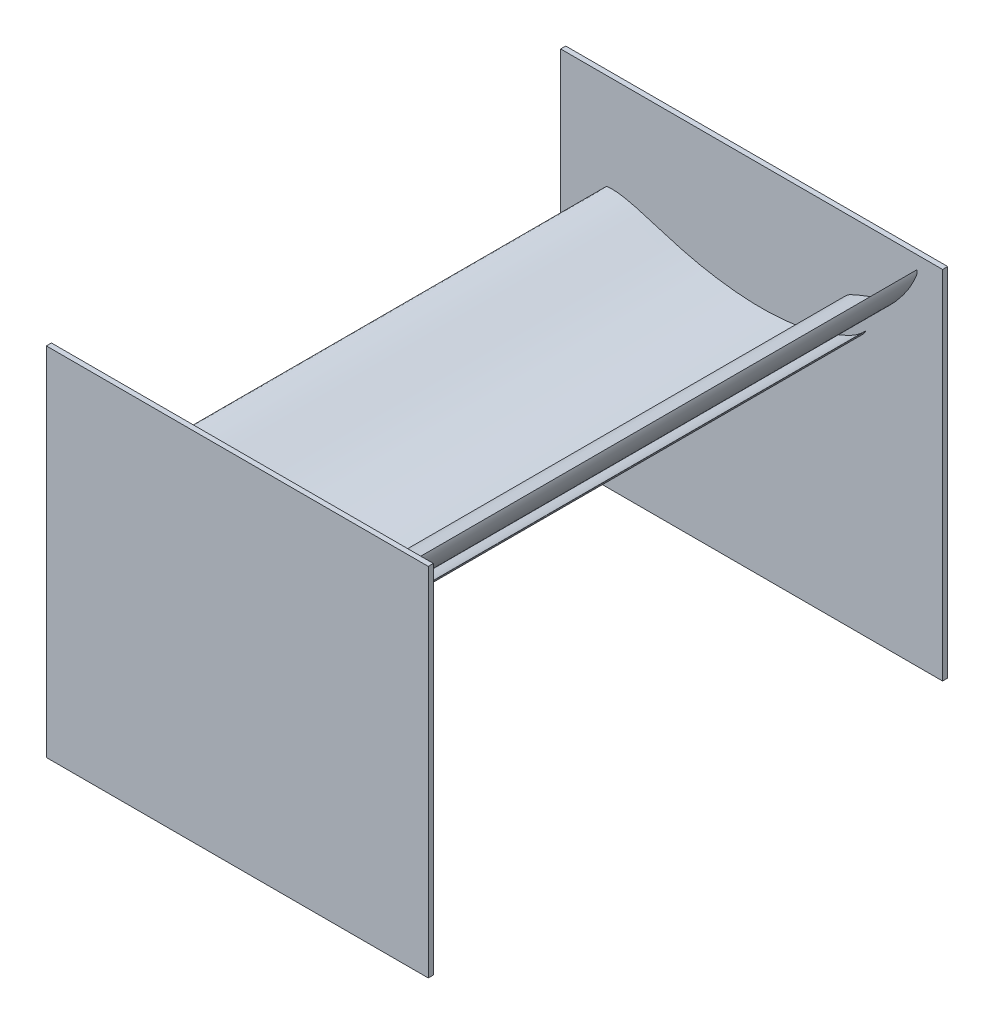
SolidWorks part; units mm, degrees
ref_plane "Front Plane" through (0, 0, 0) normal (0, 0, 1) x (1, 0, 0)
ref_plane "Top Plane" through (0, 0, 0) normal (0, 1, 0) x (1, 0, 0)
ref_plane "Right Plane" through (0, 0, 0) normal (1, 0, 0) x (0, 0, -1)
sketch "Sketch8" plane through (0, 0, 0) normal (0, 0, 1) x (1, 0, 0)
  line L0 (0, 500) -> (923, 500) construction
  line L1 (0, 0) -> (923, 0) construction
  line L2 (0, 0) -> (0, 1200) construction
  line L3 (0, 1200) -> (923, 1200) construction
  line L4 (923, 0) -> (923, 1200) construction
  line L5 (-114, 1134) -> (686, 312.7) construction
  line L6 (273, 1012.2592) -> (2273, 1012.2592) construction
  line L7 (273, 1012.2592) -> (772.9238, 1020.9854) construction
  line L8 (735.0981, 1062.2592) -> (873, 1170) construction
  line L14 (173, 1200) -> (923, 1200)
  line L15 (173, 1200) -> (173, 500)
  line L16 (173, 500) -> (923, 500)
  line L17 (923, 1200) -> (923, 500)
  circle A0 centre (-238, 828) radius 150 construction
  spline S0 degree 3 poles (736.9746, 1063.6908) (735.1551, 1062.3394) (733.9139, 1061.2588) (733.1597, 1060.5025) (732.8208, 1060.1469) (732.6556, 1059.9292) (732.5731, 1059.7929) (732.5155, 1059.6641) (732.4782, 1059.5391) (732.4573, 1059.3986) (732.455, 1059.2184) (732.4874, 1058.9473) (732.5552, 1058.6772) (732.6716, 1058.3061) (732.8406, 1057.8961) (733.1306, 1057.391) (733.4505, 1056.9645) (733.9202, 1056.4442) (734.6935, 1055.7537) (735.7648, 1055.0186) (737.0781, 1054.2035) (738.505, 1053.4345) (740.229, 1052.7358) (742.0964, 1052.1618) (744.1717, 1051.6988) (746.4576, 1051.3616) (748.9409, 1051.1771) (751.5937, 1051.1584) (754.4242, 1051.3136) (757.458, 1051.6498) (760.1779, 1052.0955) (763.0467, 1052.6889) (766.0059, 1053.4314) (769.5135, 1054.5043) (773.0726, 1055.7887) (776.6813, 1057.2897) (780.329, 1059.0097) (782.926, 1060.3776) (785.6969, 1061.9131) (788.667, 1063.651) (793.0339, 1066.396) (797.6969, 1069.5025) (802.486, 1072.9262) (807.1111, 1076.4878) (811.4917, 1080.1245) (815.743, 1083.9031) (820.0128, 1087.9518) (824.2938, 1092.2756) (828.5976, 1096.8922) (832.8951, 1101.7723) (837.2473, 1106.9902) (841.6734, 1112.5801) (845.9633, 1118.2629) (849.9689, 1123.8527) (853.6882, 1129.3444) (857.1892, 1134.858) (860.5032, 1140.4704) (863.5577, 1146.0372) (866.2414, 1151.3298) (868.4897, 1156.0946) (870.1449, 1159.938) (871.3146, 1162.9212) (872.1009, 1165.2079) (872.6215, 1167.1684) (872.9478, 1169.0316) (873.0693, 1171.0025) (873.0279, 1172.535) (872.7378, 1175.6985) (872.5696, 1171.3659) (872.0708, 1169.3953) (871.41, 1166.6231) (870.5405, 1164.0765) (869.4632, 1161.412) (868.0378, 1158.378) (865.8227, 1154.203) (863.2064, 1149.5706) (860.4497, 1144.8616) (857.9542, 1140.965) (855.3499, 1137.2162) (852.5976, 1133.5974) (849.6571, 1130.0649) (846.5891, 1126.6912) (843.3151, 1123.3813) (839.7067, 1119.9719) (835.6411, 1116.3371) (831.1866, 1112.6021) (826.52, 1108.9526) (821.6076, 1105.3813) (816.4521, 1101.8925) (810.9849, 1098.4359) (805.2753, 1095.0359) (799.3656, 1091.7292) (793.383, 1088.6209) (787.4499, 1085.7776) (781.345, 1083.0544) (774.758, 1080.3003) (767.4841, 1077.4374) (760.2624, 1074.7005) (753.8915, 1072.183) (748.9419, 1070.0767) (745.0446, 1068.283) (741.8647, 1066.6615) (739.1885, 1065.1306) (736.9746, 1063.6908) (735.1551, 1062.3394) (733.9139, 1061.2588) knots -0.020104 -0.012389 -0.005583 0 0.004865 0.006933 0.008138 0.008601 0.009012 0.009349 0.009673 0.010003 0.010428 0.011042 0.012077 0.012543 0.014005 0.015444 0.016969 0.018056 0.02078 0.024841 0.027936 0.032555 0.037166 0.042082 0.047422 0.053348 0.059667 0.066375 0.073542 0.081249 0.089615 0.094526 0.103562 0.112844 0.122456 0.132374 0.142605 0.153166 0.154726 0.166736 0.179372 0.194013 0.209411 0.224207 0.23847 0.252772 0.267526 0.283284 0.299114 0.315597 0.332811 0.350866 0.369905 0.387044 0.403244 0.420423 0.436787 0.452885 0.468783 0.481983 0.493012 0.500655 0.506382 0.511438 0.516044 0.520926 0.525831 0.529954 0.53661 0.543291 0.550106 0.557027 0.564113 0.571894 0.58258 0.600094 0.612425 0.624138 0.635332 0.647187 0.658759 0.670333 0.681913 0.694215 0.708142 0.723449 0.738488 0.75326 0.769704 0.785898 0.802526 0.820319 0.837475 0.853872 0.870428 0.888391 0.908253 0.929971 0.947221 0.960431 0.970941 0.979896 0.987611 0.994417 1 1.004865 1.006933 1.008138 only from (735.0981, 1062.2592) to (735.0981, 1062.2592)
  spline S1 degree 3 poles (279.6437, 1012.1613) (273.2655, 1012.3375) (268.6383, 1012.1063) (265.6533, 1011.7454) (264.2844, 1011.5481) (263.5398, 1011.354) (263.12, 1011.1959) (262.7685, 1011.0113) (262.4684, 1010.7994) (262.1775, 1010.5249) (261.859, 1010.1301) (261.4589, 1009.474) (261.1388, 1008.7582) (260.7505, 1007.7345) (260.4109, 1006.533) (260.1736, 1004.9107) (260.1394, 1003.4101) (260.2731, 1001.4414) (260.7826, 998.5674) (261.8739, 995.0763) (263.3617, 990.9869) (265.1807, 986.802) (267.7798, 982.2555) (270.9133, 977.7353) (274.7, 973.0991) (279.1714, 968.3745) (284.3455, 963.6446) (290.1832, 958.9864) (296.7171, 954.4038) (304.0156, 949.8678) (310.8099, 946.1205) (318.1911, 942.441) (326.0315, 938.9339) (335.6606, 935.2036) (345.7718, 931.8517) (356.3698, 928.8928) (367.435, 926.3507) (375.5627, 924.8581) (384.3665, 923.4335) (393.9635, 922.1102) (408.4041, 920.5846) (424.1293, 919.3439) (440.6854, 918.5854) (457.1186, 918.4174) (473.1415, 918.8411) (489.1253, 919.8041) (505.6199, 921.3324) (522.6183, 923.4499) (540.1765, 926.1759) (558.1795, 929.4957) (576.8913, 933.4677) (596.4142, 938.1347) (615.7972, 943.2441) (634.3892, 948.6424) (652.177, 954.322) (669.5201, 960.43) (686.6213, 967.082) (703.0684, 974.0847) (718.2182, 981.1259) (731.486, 987.7572) (741.8375, 993.3814) (749.6176, 997.9472) (755.3374, 1001.639) (759.9012, 1005.0713) (763.866, 1008.6265) (767.5651, 1012.7764) (770.1404, 1016.2396) (775.004, 1023.745) (767.0917, 1014.4501) (762.5584, 1010.9576) (756.2714, 1005.973) (749.9154, 1001.8509) (742.8943, 997.8295) (734.4599, 993.5964) (722.292, 988.2128) (708.4404, 982.5151) (694.145, 976.8922) (681.8412, 972.6128) (669.5539, 968.8494) (657.1655, 965.6316) (644.5109, 962.9319) (631.8504, 960.8057) (618.8447, 959.1792) (604.9264, 957.9145) (589.6038, 956.9467) (573.2462, 956.434) (556.5683, 956.4798) (539.4825, 957.126) (522.0023, 958.3781) (503.8883, 960.2442) (485.3364, 962.657) (466.5042, 965.6246) (447.856, 969.1581) (429.7783, 973.1918) (411.5296, 977.7904) (392.1604, 983.1597) (371.0816, 989.4835) (350.3376, 995.9954) (331.8583, 1001.5123) (317.2398, 1005.4653) (305.4937, 1008.2787) (295.6352, 1010.2246) (287.0486, 1011.4945) (279.6437, 1012.1613) (273.2655, 1012.3375) (268.6383, 1012.1063) knots -0.020104 -0.012389 -0.005583 0 0.004865 0.006933 0.008138 0.008601 0.009012 0.009349 0.009673 0.010003 0.010428 0.011042 0.012077 0.012543 0.014005 0.015444 0.016969 0.018056 0.02078 0.024841 0.027936 0.032555 0.037166 0.042082 0.047422 0.053348 0.059667 0.066375 0.073542 0.081249 0.089615 0.094526 0.103562 0.112844 0.122456 0.132374 0.142605 0.153166 0.154726 0.166736 0.179372 0.194013 0.209411 0.224207 0.23847 0.252772 0.267526 0.283284 0.299114 0.315597 0.332811 0.350866 0.369905 0.387044 0.403244 0.420423 0.436787 0.452885 0.468783 0.481983 0.493012 0.500655 0.506382 0.511438 0.516044 0.520926 0.525831 0.529954 0.53661 0.543291 0.550106 0.557027 0.564113 0.571894 0.58258 0.600094 0.612425 0.624138 0.635332 0.647187 0.658759 0.670333 0.681913 0.694215 0.708142 0.723449 0.738488 0.75326 0.769704 0.785898 0.802526 0.820319 0.837475 0.853872 0.870428 0.888391 0.908253 0.929971 0.947221 0.960431 0.970941 0.979896 0.987611 0.994417 1 1.004865 1.006933 1.008138 only from (273, 1012.2592) to (273, 1012.2592)
  point P4 (-114, 1134)
  point P8 (0, 828)
  point P9 (686, 312.7)
  point P11 (772.9238, 1020.9854)
  point P22 (873, 1170)
  dimension "D9" = 300
  dimension "D1" = 1200
  dimension "D2" = 923
  dimension "D3" = 500
  dimension "D4" = 828
  dimension "D5" = 114
  dimension "D6" = 306
  dimension "D7" = 821.3
  dimension "D8" = 800
  dimension "D10" = 238
  dimension "D11" = 500
  dimension "D12" = 175
  dimension "D13" = 600
  dimension "D14" = 50
  dimension "D15" = 1
  dimension "D16" = 38
  dimension "D17" = 2000
  dimension "D18" = 30
  dimension "D19" = 50
  dimension "D20" = 750
  dimension "D21" = 700
extrude "Boss-Extrude4" add sketch "Sketch8" along normal blind 1000 contours S1 | S0
extrude "Boss-Extrude6" add sketch "Sketch8<4>" against normal blind 10 contours S1 | L17 L14 L15 L16 S1 S0 | S0 region at (553.1107, 837.5068, 0) region at (749.3567, 998.4627, 0)
sketch "Sketch8<4>" plane through (0, 0, 0) normal (0, 0, 1) x (1, 0, 0) same geometry as "Sketch8"
ref_plane "Plane1" through (0, 0, 500) normal (0, 0, 1) x (1, 0, 0)
mirror "Mirror1" about plane through (0, 0, 500) normal (0, 0, 1) of "Boss-Extrude6"
